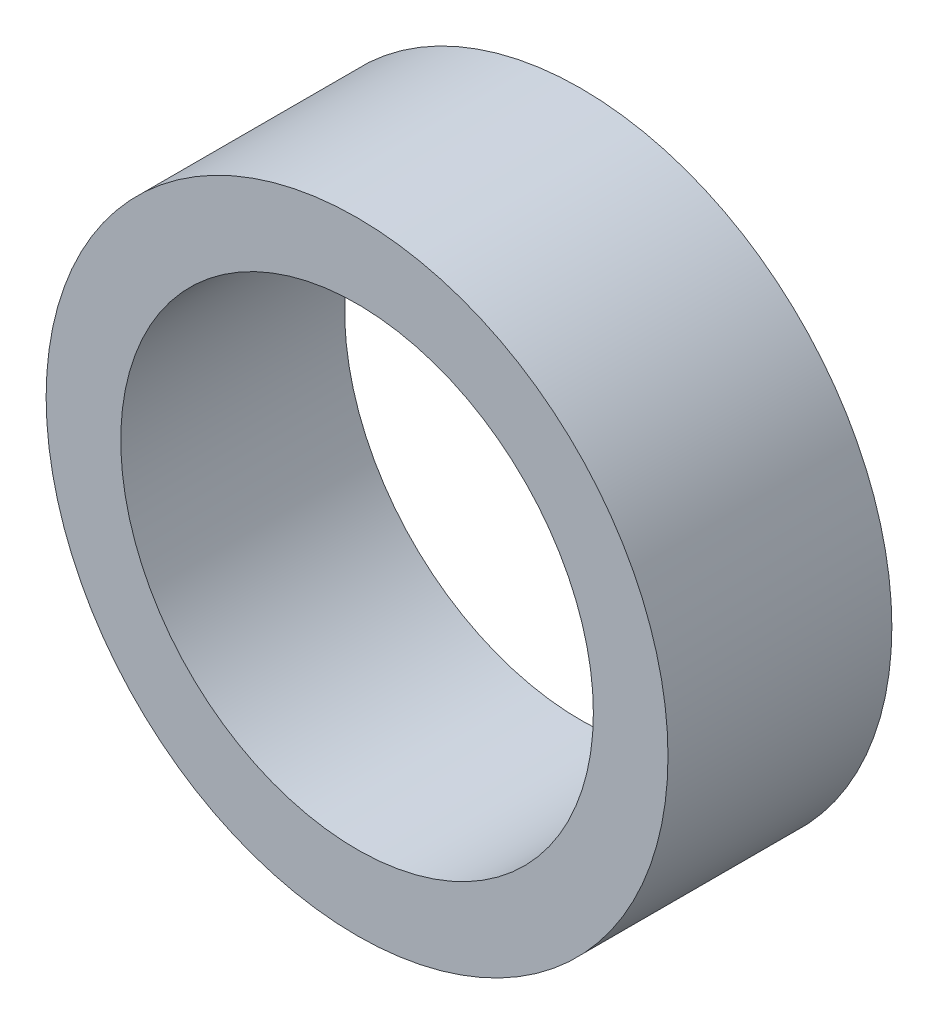
SolidWorks part; units mm, degrees
ref_plane "正面" through (0, 0, 0) normal (0, 0, 1) x (1, 0, 0)
ref_plane "平面" through (0, 0, 0) normal (0, 1, 0) x (1, 0, 0)
ref_plane "右側面" through (0, 0, 0) normal (1, 0, 0) x (0, 0, -1)
sketch "ｽｹｯﾁ1" plane through (0, 0, 0) normal (0, 0, 1) x (1, 0, 0)
  circle A0 centre (0, 0) radius 2.5
  circle A1 centre (0, 0) radius 1.9
  dimension "D1" = 5
  dimension "D2" = 3.8
extrude "ﾎﾞｽ - 押し出し1" add sketch "ｽｹｯﾁ1" along normal blind 1.8
